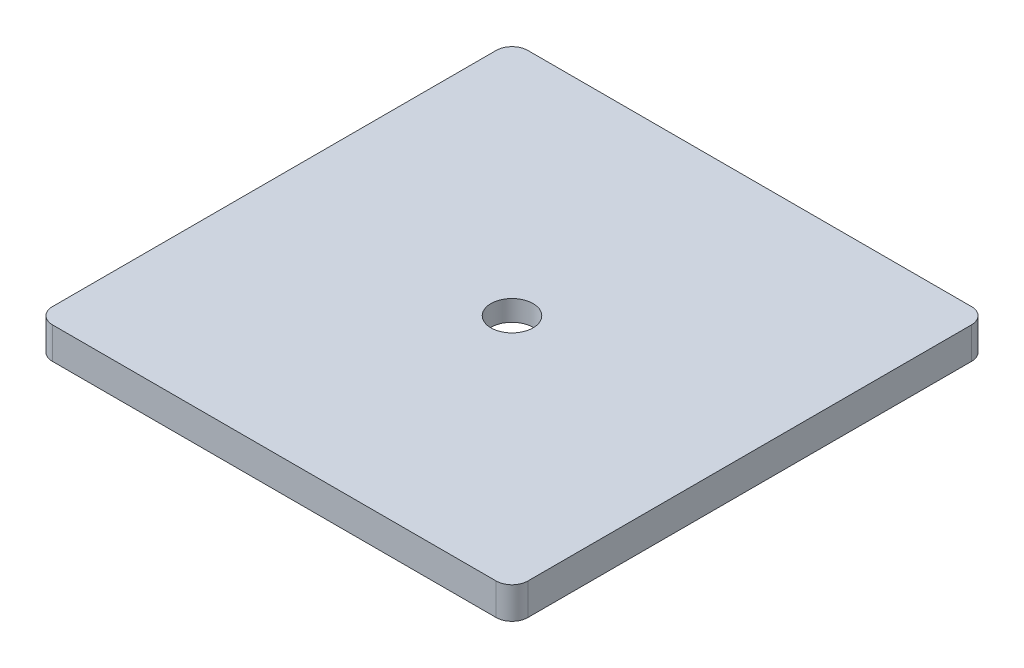
SolidWorks part; units mm, degrees
ref_plane "Front Plane" through (0, 0, 0) normal (0, 0, 1) x (1, 0, 0)
ref_plane "Top Plane" through (0, 0, 0) normal (0, 1, 0) x (1, 0, 0)
ref_plane "Right Plane" through (0, 0, 0) normal (1, 0, 0) x (0, 0, -1)
sketch "Sketch1" plane through (0, 0, 0) normal (0, 1, 0) x (1, 0, 0)
  line L1 (-38.1, 38.1) -> (38.1, 38.1)
  line L2 (-38.1, 38.1) -> (-38.1, -38.1)
  line L3 (-38.1, -38.1) -> (38.1, -38.1)
  line L4 (38.1, 38.1) -> (38.1, -38.1)
  line L5 (-38.1, 38.1) -> (38.1, -38.1) construction
  line L6 (-38.1, -38.1) -> (38.1, 38.1) construction
  point P0 (0, 0)
  dimension "D1" = 76.2
  dimension "D2" = 76.2
extrude "Boss-Extrude1" add sketch "Sketch1" along normal blind 5.08
fillet "Fillet1" radius 2.54 4 edges at (-38.1, 2.54, -38.1) (38.1, 2.54, -38.1) (-38.1, 2.54, 38.1) (38.1, 2.54, 38.1)
sketch "Sketch2" plane through (0, 0, 0) normal (0, -1, 0) x (1, 0, 0)
  line L1 (-17.5895, 17.5895) -> (17.5895, 17.5895)
  line L2 (-17.5895, 17.5895) -> (-17.5895, -17.5895)
  line L3 (-17.5895, -17.5895) -> (17.5895, -17.5895)
  line L4 (17.5895, 17.5895) -> (17.5895, -17.5895)
  line L5 (-17.5895, 17.5895) -> (17.5895, -17.5895) construction
  line L6 (-17.5895, -17.5895) -> (17.5895, 17.5895) construction
  point P0 (0, 0)
  dimension "D1" = 35.179
ref_plane "Plane1" through (0, -8.89, 0) normal (0, -1, 0) x (-1, 0, 0)
sketch "Sketch3" plane through (0, -8.89, 0) normal (0, -1, 0) x (-1, 0, 0)
  line L1 (-21.717, 22.098) -> (21.717, 22.098)
  line L2 (-21.717, 22.098) -> (-21.717, -22.098)
  line L3 (-21.717, -22.098) -> (21.717, -22.098)
  line L4 (21.717, 22.098) -> (21.717, -22.098)
  line L5 (-21.717, 22.098) -> (21.717, -22.098) construction
  line L6 (-21.717, -22.098) -> (21.717, 22.098) construction
  point P0 (0, 0)
  dimension "D1" = 44.196
  dimension "D2" = 43.434
extrude "Boss-Extrude2" add sketch "Sketch3" against normal blind 1.397 separate body
sketch "Sketch4" plane through (0, -7.493, 0) normal (0, 1, 0) x (1, 0, 0)
  line L4 (-21.717, 22.098) -> (-21.717, -22.098)
  line L5 (-21.717, -22.098) -> (21.717, -22.098)
  line L6 (21.717, -22.098) -> (21.717, 22.098)
  line L7 (21.717, 22.098) -> (-21.717, 22.098)
  line L8 (-21.717, 22.098) -> (-21.717, -22.098)
  line L9 (-21.717, -22.098) -> (21.717, -22.098)
  line L10 (21.717, -22.098) -> (21.717, 22.098)
  line L11 (21.717, 22.098) -> (-21.717, 22.098)
  dimension "D1" = 0
loft "Loft1" add profiles "Sketch2", "Sketch4" connector at (17.5895, 0, 17.5895) connector at (21.717, -7.493, 22.098)
shell "Shell1" thickness 3.302 removed face at (0, -8.89, 0)
hole_wizard "1/4 Clearance Hole1" positions "Sketch5" profile "Sketch6" hole size "1/4" standard "ANSI Inch" end condition through all
sketch "Sketch5" plane through (0, 1.778, 0) normal (0, -1, 0) x (-1, 0, 0)
  point P0 (0, 0)
sketch "Sketch6" plane through (0, 1.778, 0) normal (1, 0, 0) x (0, 0, -1)
  line L0 (0, 0) -> (0, 3.302)
  line L1 (0, 3.302) -> (3.3782, 3.302)
  line L2 (3.3782, 3.302) -> (3.3782, 0)
  line L5 (3.3782, 0) -> (0, 0)
  line L11 (0, -6.35) -> (0, 107.95) construction
  dimension "Thru Hole Dia." = 6.7564
  dimension "Thru Hole Depth" = 3.302
